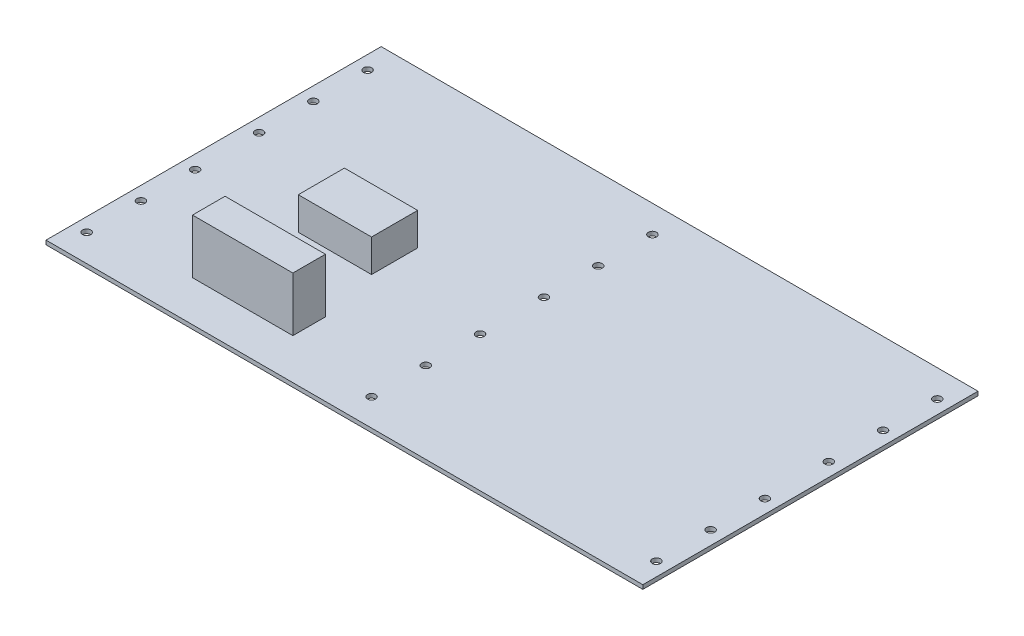
SolidWorks part; units mm, degrees
ref_plane "前视基准面" through (0, 0, 0) normal (0, 0, 1) x (1, 0, 0)
ref_plane "上视基准面" through (0, 0, 0) normal (0, 1, 0) x (1, 0, 0)
ref_plane "右视基准面" through (0, 0, 0) normal (1, 0, 0) x (0, 0, -1)
sketch "草图1" plane through (0, 0, 0) normal (0, 1, 0) x (1, 0, 0)
  line L1 (-65.705, 44.3173) -> (154.295, 44.3173)
  line L2 (-65.705, 44.3173) -> (-65.705, -79.2327)
  line L3 (-65.705, -79.2327) -> (154.295, -79.2327)
  line L4 (154.295, 44.3173) -> (154.295, -79.2327)
  dimension "D1" = 123.55
  dimension "D2" = 220
extrude "凸台-拉伸1" add sketch "草图1" along normal blind 1.5
sketch "草图2" plane through (0, 1.5, 0) normal (0, 1, 0) x (1, 0, 0)
  line L1 (154.295, -79.2327) -> (154.295, 44.3173) construction
  line L2 (-65.705, -17.4577) -> (154.295, -17.4577)
  line L3 (-65.705, 44.3173) -> (-65.705, -79.2327) construction
  line L5 (-65.705, -79.2327) -> (154.295, -79.2327) construction
  circle A0 centre (149.295, -69.2327) radius 1.5
  circle A1 centre (44.295, -69.2327) radius 1.5
  circle A2 centre (-60.705, -69.2327) radius 1.5
  circle A3 centre (44.295, -49.2327) radius 1.5
  circle A4 centre (-60.705, -49.2327) radius 1.5
  circle A5 centre (149.295, -49.2327) radius 1.5
  circle A6 centre (149.295, 14.3173) radius 1.5
  circle A7 centre (-60.705, 14.3173) radius 1.5
  circle A8 centre (44.295, 14.3173) radius 1.5
  circle A9 centre (-60.705, 34.3173) radius 1.5
  circle A10 centre (44.295, 34.3173) radius 1.5
  circle A11 centre (149.295, 34.3173) radius 1.5
  circle A12 centre (149.295, -29.2327) radius 1.5
  circle A13 centre (44.295, -29.2327) radius 1.5
  circle A14 centre (-60.705, -29.2327) radius 1.5
  circle A15 centre (149.295, -5.6827) radius 1.5
  circle A16 centre (44.295, -5.6827) radius 1.5
  circle A17 centre (-60.705, -5.6827) radius 1.5
  point P44 (0, 0)
  dimension "D2" = 5
  dimension "D3" = 3
  dimension "D1" = 10
  dimension "D4" = 3
  dimension "D5" = 3
extrude "切除-拉伸1" cut sketch "草图2" against normal blind 10 contours A0 | A5 | A3 | A1 | A8 | A10 | A6 | A11 | A9 | A7 | A4 | A2 | A14 | A17 | A16 | A13 | A15 | A12 region at (149.295, 1.5, 69.2327) region at (44.295, 1.5, 69.2327) region at (-60.705, 1.5, 69.2327) region at (44.295, 1.5, 49.2327) region at (-60.705, 1.5, 49.2327) region at (149.295, 1.5, 49.2327) region at (149.295, 1.5, -14.3173) region at (-60.705, 1.5, -14.3173) region at (44.295, 1.5, -14.3173) region at (-60.705, 1.5, -34.3173) region at (44.295, 1.5, -34.3173) region at (149.295, 1.5, -34.3173) region at (149.295, 1.5, 29.2327) region at (44.295, 1.5, 29.2327) region at (-60.705, 1.5, 29.2327) region at (149.295, 1.5, 5.6827) region at (44.295, 1.5, 5.6827) region at (-60.705, 1.5, 5.6827)
sketch "草图3" plane through (0, 1.5, 0) normal (0, 1, 0) x (1, 0, 0)
  line L0 (-25.705, -63.2327) -> (-25.705, -53.2327)
  line L1 (-65.705, -79.2327) -> (154.295, -79.2327) construction
  line L4 (-65.705, 44.3173) -> (-65.705, -79.2327) construction
  line L5 (-25.705, -63.2327) -> (9.295, -63.2327)
  line L6 (-25.705, -53.2327) -> (9.295, -53.2327)
  line L10 (9.295, -53.2327) -> (9.295, -63.2327)
  line L12 (-20.705, -14.2327) -> (-20.705, -29.2327)
  line L13 (-20.705, -14.2327) -> (4.295, -14.2327)
  line L14 (-20.705, -29.2327) -> (4.295, -29.2327)
  line L15 (4.295, -14.2327) -> (4.295, -29.2327)
  line L16 (-21.705, -13.2327) -> (5.295, -13.2327)
  line L17 (5.295, -13.2327) -> (5.295, -30.2327)
  line L18 (-21.705, -30.2327) -> (5.295, -30.2327)
  line L19 (-21.705, -13.2327) -> (-21.705, -30.2327)
  line L20 (-26.705, -52.2327) -> (10.295, -52.2327)
  line L21 (10.295, -52.2327) -> (10.295, -64.2327)
  line L22 (-26.705, -64.2327) -> (10.295, -64.2327)
  line L23 (-26.705, -64.2327) -> (-26.705, -52.2327)
  point P18 (-8.205, -53.2327)
  dimension "D1" = 40
  dimension "D2" = 75
  dimension "D3" = 16
  dimension "D4" = 26
  dimension "D5" = 45
  dimension "D6" = 50
  dimension "D7" = 65
  dimension "D8" = 70
  dimension "D9" = 1
  dimension "D10" = 1
extrude "切除-拉伸2" cut sketch "草图3" against normal through all contours L15 L14 L12 L13 | L6 L10 L5 L0
extrude "凸台-拉伸2" add sketch "草图3<3>" along normal blind 12 contours L16 L19 L18 L17 L13 L15 L14 L12 region at (-8.205, 1.5, 13.5518)
sketch "草图3<3>" plane through (0, 1.5, 0) normal (0, 1, 0) x (1, 0, 0) same geometry as "草图3"
extrude "凸台-拉伸3" add sketch "草图3<4>" along normal blind 20 contours L23 L22 L21 L20 L6 L10 L5 L0 region at (-8.205, 1.5, 52.6217)
sketch "草图3<4>" plane through (0, 1.5, 0) normal (0, 1, 0) x (1, 0, 0) same geometry as "草图3"
sketch "草图11" plane through (-20.705, 0, 0) normal (1, 0, 0) x (0, 0, -1)
  line L0 (-30.2327, 13.5) -> (-13.2327, 13.5)
  line L1 (-13.2327, 13.5) -> (-13.2327, 12.5)
  line L2 (-13.2327, 13.5) -> (-13.2327, 1.5) construction
  line L3 (-13.2327, 12.5) -> (-30.2327, 12.5)
  line L4 (-30.2327, 13.5) -> (-30.2327, 1.5) construction
  line L5 (-30.2327, 12.5) -> (-30.2327, 13.5)
  dimension "D1" = 1
extrude "凸台-拉伸4" add sketch "草图11" along normal up to surface (25 mm away) up to face at (4.295, 6.75, 21.7327)
sketch "草图12" plane through (-25.705, 0, 0) normal (1, 0, 0) x (0, 0, -1)
  line L0 (-64.2327, 21.5) -> (-52.2327, 21.5)
  line L1 (-52.2327, 21.5) -> (-52.2327, 20.5)
  line L2 (-52.2327, 21.5) -> (-52.2327, 1.5) construction
  line L3 (-52.2327, 20.5) -> (-64.2327, 20.5)
  line L4 (-64.2327, 21.5) -> (-64.2327, 1.5) construction
  line L5 (-64.2327, 20.5) -> (-64.2327, 21.5)
  dimension "D1" = 1
extrude "凸台-拉伸5" add sketch "草图12" along normal up to surface (35 mm away) up to face at (9.295, 10.75, 58.2327)
